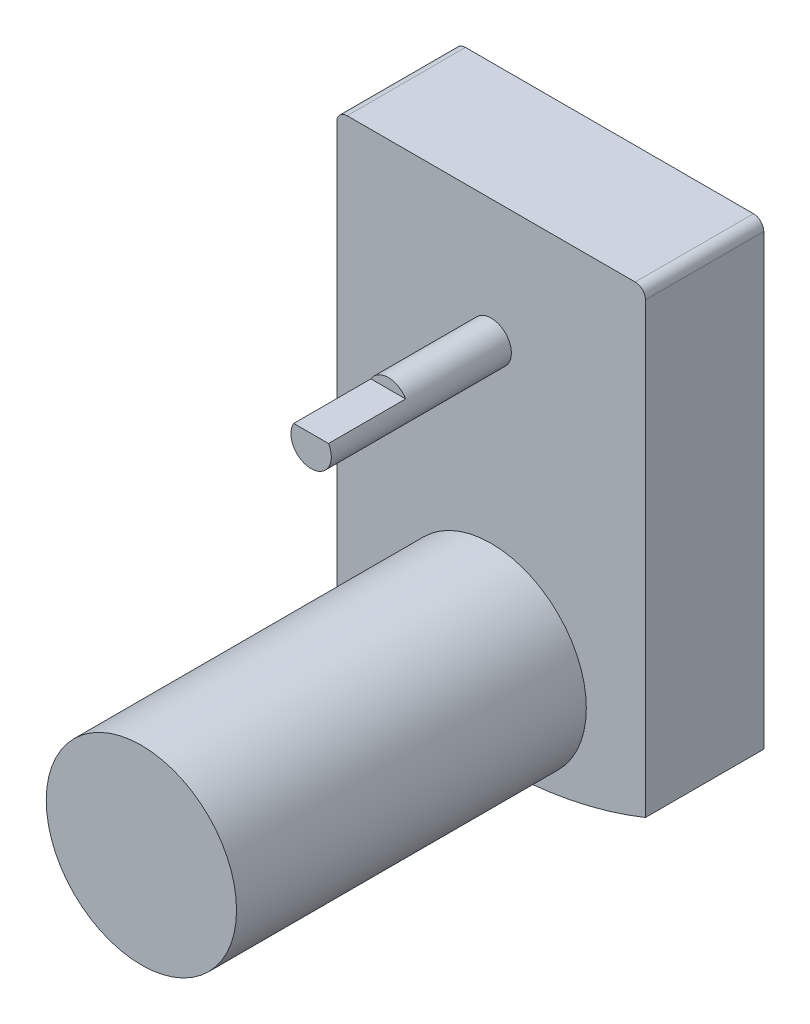
SolidWorks part; units mm, degrees
ref_plane "前视基准面" through (0, 0, 0) normal (0, 0, 1) x (1, 0, 0)
ref_plane "上视基准面" through (0, 0, 0) normal (0, 1, 0) x (1, 0, 0)
ref_plane "右视基准面" through (0, 0, 0) normal (1, 0, 0) x (0, 0, -1)
sketch "草图3" plane through (0, 0, 0) normal (0, 0, 1) x (1, 0, 0)
  line L1 (-30, 47.5) -> (30, 47.5)
  line L2 (-30, 47.5) -> (-30, -47.5)
  line L3 (-30, -47.5) -> (30, -47.5)
  line L4 (30, 47.5) -> (30, -47.5)
  line L5 (-30, 47.5) -> (30, -47.5) construction
  line L6 (-30, -47.5) -> (30, 47.5) construction
  point P0 (0, 0)
  dimension "D1" = 60
  dimension "D2" = 95
extrude "凸台-拉伸1" add sketch "草图3" along normal blind 23
sketch "草图4" plane through (0, 0, 23) normal (0, 0, 1) x (1, 0, 0)
  line L0 (0, -47.5) -> (0, -29) construction
  line L1 (-30, -47.5) -> (30, -47.5) construction
  circle A0 centre (0, -29) radius 18.5
  dimension "D1" = 18.5
extrude "凸台-拉伸2" add sketch "草图4" along normal blind 68 contours A0
sketch "草图5" plane through (0, 0, 23) normal (0, 0, 1) x (1, 0, 0)
  line L0 (0, 47.5) -> (0, 23.5) construction
  line L1 (30, 47.5) -> (-30, 47.5) construction
  line L2 (-3.928, 23.5) -> (3.928, 23.5) construction
  circle A0 centre (0, 23.5) radius 3.928
extrude "凸台-拉伸3" add sketch "草图5" along normal blind 35 contours A0
sketch "草图6" plane through (0, 0, 58) normal (0, 0, 1) x (1, 0, 0)
  line L0 (-3.928, 23.5) -> (3.928, 23.5) construction
  line L1 (-3.928, 25.5) -> (3.928, 25.5)
  line L2 (-3.928, 25.5) -> (-0.4217, 30.8502)
  line L3 (-0.4217, 30.8502) -> (3.928, 25.5)
  circle A0 centre (0, 23.5) radius 3.928 construction
  circle A1 centre (0, 23.5) radius 3.928 construction
  dimension "D1" = 2
extrude "切除-拉伸4" cut sketch "草图6" against normal blind 15
sketch "草图7" plane through (0, 0, 0) normal (0, 0, -1) x (-1, 0, 0)
  line L0 (0, 47.5) -> (0, 23.5) construction
  line L1 (-30, 47.5) -> (30, 47.5) construction
  line L2 (0, 23.5) -> (20, 23.5) construction
  circle A0 centre (20, 23.5) radius 2
  circle A1 centre (20, 23.5) radius 4
  circle A2 centre (-20, 23.5) radius 4
  circle A3 centre (-20, 23.5) radius 2
  circle A4 centre (20, -16.5) radius 4
  circle A5 centre (-20, -16.5) radius 4
  circle A6 centre (20, -16.5) radius 2
  circle A7 centre (-20, -16.5) radius 2
  dimension "D1" = 2
extrude "凸台-拉伸5" add sketch "草图7" along normal blind 5
fillet "圆角1" radius 2 1 edges at (-30, 47.5, 11.5)
fillet "圆角2" radius 2 1 edges at (30, 47.5, 11.5)
sketch "草图8" plane through (0, 0, 0) normal (0, 0, -1) x (-1, 0, 0)
  line L0 (0, -47.5) -> (0, 32.5) construction
  line L1 (30, -47.5) -> (-30, -47.5) construction
  line L2 (-58.1035, -22.4908) -> (-70.6967, -61.4153)
  line L3 (-70.6967, -61.4153) -> (7.4719, -106.9022)
  line L4 (7.4719, -106.9022) -> (82.7736, -42.1121)
  line L5 (82.7736, -42.1121) -> (69.3696, -7.348)
  arc A0 (-58.1035, -22.4908) -> (69.3696, -7.348) centre (0, 32.5) ccw
extrude "切除-拉伸5" cut sketch "草图8" against normal blind 18
extrude "切除-拉伸6" cut sketch "草图8<2>" against normal blind 50
sketch "草图8<2>" plane through (0, 0, 0) normal (0, 0, -1) x (-1, 0, 0) same geometry as "草图8"
